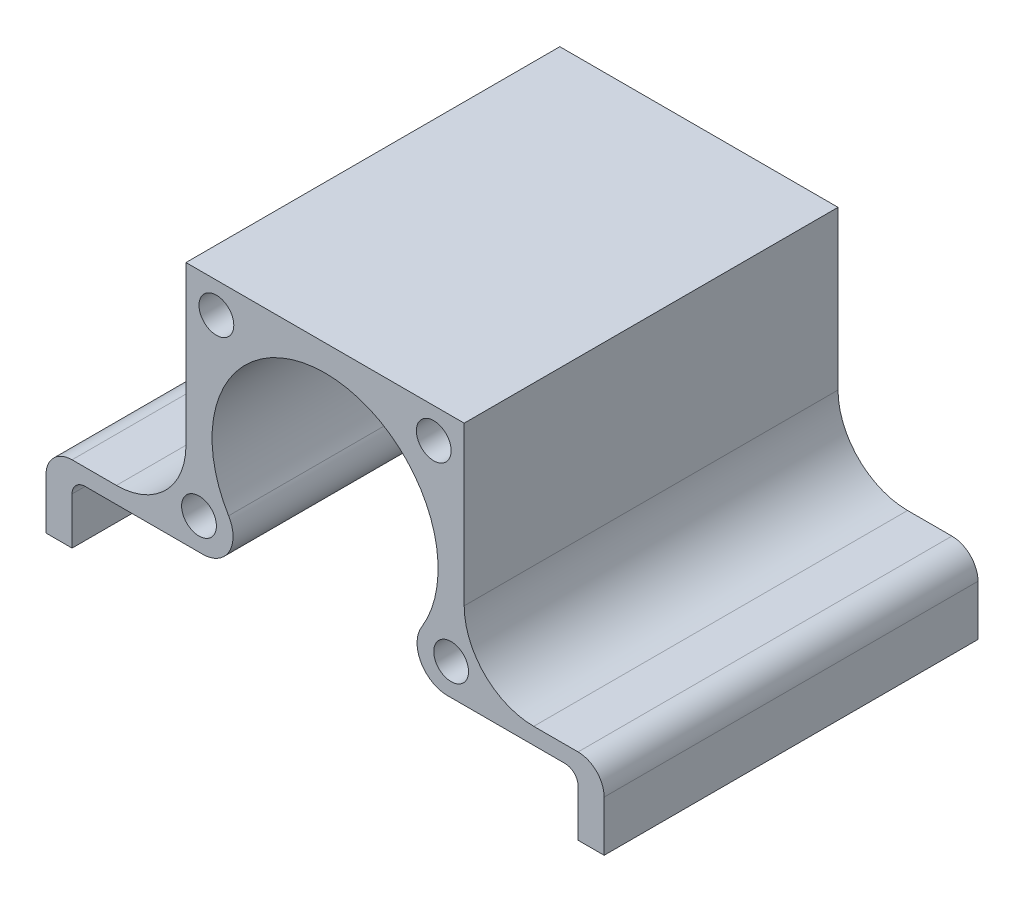
SolidWorks part; units mm, degrees
ref_plane "Front Plane" through (0, 0, 0) normal (0, 0, 1) x (1, 0, 0)
ref_plane "Top Plane" through (0, 0, 0) normal (0, 1, 0) x (1, 0, 0)
ref_plane "Right Plane" through (0, 0, 0) normal (1, 0, 0) x (0, 0, -1)
sketch "Sketch1" plane through (0, 0, 0) normal (0, 0, 1) x (1, 0, 0)
  line L0 (-16, 38) -> (16, 38)
  line L1 (-20.1, 6.5) -> (20.1, 6.5) construction
  line L2 (-20.1, 6.5) -> (-20.1, 2.3) construction
  line L3 (-20.1, 2.3) -> (20.1, 2.3) construction
  line L4 (20.1, 6.5) -> (20.1, 2.3) construction
  line L5 (-20.1, 6.5) -> (20.1, 2.3) construction
  line L6 (-20.1, 2.3) -> (20.1, 6.5) construction
  line L7 (-26.1, 7) -> (26.1, 7) construction
  line L8 (-26.1, 7) -> (-26.1, 1.8) construction
  line L9 (-26.1, 1.8) -> (26.1, 1.8) construction
  line L10 (26.1, 7) -> (26.1, 1.8) construction
  line L11 (-26.1, 7) -> (26.1, 1.8) construction
  line L12 (-26.1, 1.8) -> (26.1, 7) construction
  line L13 (29.1, 9.9) -> (-29.1, 9.9) construction
  line L14 (29.1, 9.9) -> (29.1, -1.1) construction
  line L15 (29.1, -1.1) -> (-29.1, -1.1) construction
  line L16 (-29.1, 9.9) -> (-29.1, -1.1) construction
  line L17 (29.1, 9.9) -> (-29.1, -1.1) construction
  line L18 (29.1, -1.1) -> (-29.1, 9.9) construction
  line L19 (32.1, 11.8) -> (-32.1, 11.8) construction
  line L20 (32.1, 11.8) -> (32.1, -3) construction
  line L21 (32.1, -3) -> (-32.1, -3) construction
  line L22 (-32.1, 11.8) -> (-32.1, -3) construction
  line L23 (32.1, 11.8) -> (-32.1, -3) construction
  line L24 (32.1, -3) -> (-32.1, 11.8) construction
  line L25 (16, 38) -> (16, 11.8)
  line L26 (-16, 38) -> (-16, 11.8)
  line L27 (-16, 11.8) -> (-32.1, 11.8)
  line L28 (-32.1, 11.8) -> (-32.1, 3)
  line L29 (-32.1, 3) -> (-29.1, 3)
  line L30 (-29.1, 3) -> (-29.1, 9.9)
  line L31 (-29.1, 9.9) -> (29.1, 9.9)
  line L32 (29.1, 9.9) -> (29.1, 3)
  line L33 (29.1, 3) -> (32.1, 3)
  line L34 (32.1, 3) -> (32.1, 11.8)
  line L35 (32.1, 11.8) -> (16, 11.8)
  line L37 (-21, 6.9) -> (21, 6.9) construction
  line L38 (-21, 6.9) -> (-21, 1.9) construction
  line L39 (-21, 1.9) -> (21, 1.9) construction
  line L40 (21, 6.9) -> (21, 1.9) construction
  line L41 (-21, 6.9) -> (21, 1.9) construction
  line L42 (-21, 1.9) -> (21, 6.9) construction
  circle A0 centre (0, 22) radius 8 construction
  circle A1 centre (0, 22) radius 13
  point P2 (0, 4.4)
  point P5 (0, 4.4)
  point P13 (0, 4.4)
  point P18 (0, 4.4)
  point P34 (0, 4.4)
  dimension "D1" = 16
  dimension "D11" = 26
  dimension "D2" = 40.2
  dimension "D3" = 4.2
  dimension "D4" = 6
  dimension "D5" = 0.5
  dimension "D6" = 3
  dimension "D7" = 1.9
  dimension "D8" = 3
  dimension "D9" = 8.8
  dimension "D10" = 3
  dimension "D12" = 22
  dimension "D13" = 16
  dimension "D14" = 32
  dimension "D15" = 16
  dimension "D17" = 42
  dimension "D18" = 5
  dimension "D19" = 6
extrude "Boss-Extrude1" add sketch "Sketch1" along normal blind 43 contours A1 L31 L32 L33 L34 L35 L25 L0 L26 L27 L28 L29 L30 region at (0, 37.2688, 0)
fillet "Fillet3" radius 8 2 edges at (16, 11.8, 21.5) (-16, 11.8, 21.5)
sketch "Sketch5" plane through (0, 0, 0) normal (0, 0, -1) x (-1, 0, 0)
  line L3 (16, 38) -> (-16, 38) construction
  line L4 (-16, 38) -> (-16, 19.8) construction
  line L5 (16, 38) -> (16, 19.8) construction
  circle A0 centre (-12.5, 34.5) radius 2
  circle A1 centre (12.5, 34.5) radius 2
  circle A2 centre (-14.5, 13.5) radius 2
  circle A3 centre (14.5, 13.5) radius 2
  dimension "D1" = 4
  dimension "D5" = 24.5
  dimension "D2" = 3.5
  dimension "D3" = 3.5
  dimension "D4" = 3.5
  dimension "D6" = 1.5
  dimension "D7" = 1.5
extrude "Cut-Extrude5" cut sketch "Sketch5" against normal up to next
fillet "Fillet1" radius 1.5 2 edges at (29.1, 9.9, 21.5) (-29.1, 9.9, 21.5)
fillet "Fillet2" radius 3 2 edges at (32.1, 11.8, 21.5) (-32.1, 11.8, 21.5)
fillet "Fillet4" radius 3.5 2 edges at (-4.7529, 9.9, 21.5) (4.7529, 9.9, 21.5)
